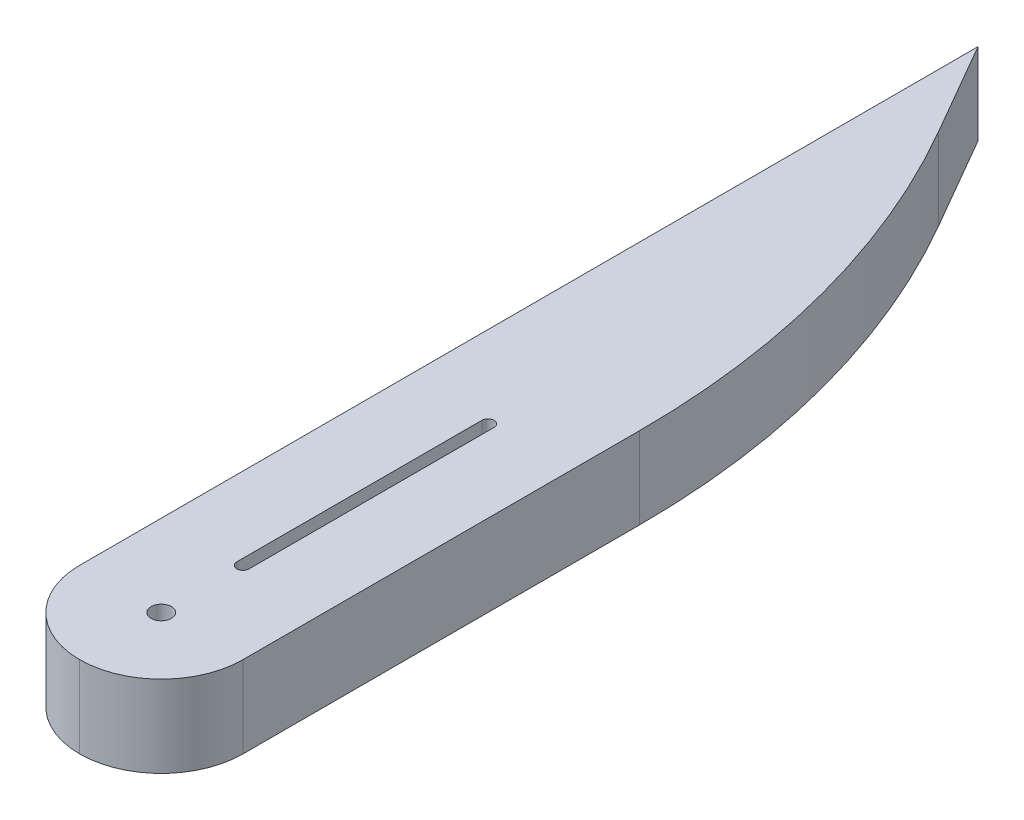
SolidWorks part; units mm, degrees
ref_plane "Front" through (0, 0, 0) normal (0, 0, 1) x (1, 0, 0)
ref_plane "Top" through (0, 0, 0) normal (0, 1, 0) x (1, 0, 0)
ref_plane "Right" through (0, 0, 0) normal (1, 0, 0) x (0, 0, -1)
sketch "Sketch1" plane through (0, 0, 0) normal (0, 0, 1) x (1, 0, 0)
  line L1 (0, 0) -> (-50.8, 0)
  line L2 (0, 0) -> (0, 25.4)
  line L3 (0, 25.4) -> (-50.8, 25.4)
  line L4 (-50.8, 0) -> (-50.8, 25.4)
  dimension "D1" = 50.8
  dimension "D2" = 25.4
extrude "Boss-Extrude1" add sketch "Sketch1" along normal blind 304.8
fillet "Fillet1" radius 25.4 2 edges at (0, 12.7, 304.8) (-50.8, 12.7, 304.8)
sketch "Sketch4" plane through (-50.8, 0, 0) normal (-1, 0, 0) x (0, 0, 1)
  line L0 (0, 25.4) -> (0, 0) construction
  line L1 (304.8, 25.4) -> (279.4, 25.4) construction
  point P0 (0, 12.7)
sketch "Sketch6" plane through (0, 25.4, 0) normal (0, 1, 0) x (1, 0, 0)
  line L0 (-50.8, 0) -> (0, -87.9882)
  line L1 (0, -279.4) -> (0, 0) construction
  line L2 (0, 0) -> (-50.8, 0) construction
  line L3 (0, -87.9882) -> (0, 0)
  line L4 (0, 0) -> (-50.8, 0)
  dimension "D1" = 60
extrude "Cut-Extrude1" cut sketch "Sketch6" against normal through all
fillet "Fillet2" radius 254 1 edges at (0, 12.7, 87.9882)
sketch "Sketch7" plane through (0, 25.4, 0) normal (0, 1, 0) x (1, 0, 0)
  circle A0 centre (-25.4, -279.4) radius 3.175
  arc A1 (-25.4, -304.8) -> (0, -279.4) centre (-25.4, -279.4) ccw construction
  dimension "D1" = 6.35
extrude "Cut-Extrude2" cut sketch "Sketch7" against normal through all
sketch "Sketch8" plane through (0, 25.4, 0) normal (0, 1, 0) x (1, 0, 0)
  line L0 (-27.305, -254) -> (-27.305, -177.8)
  line L1 (-23.495, -254) -> (-23.495, -177.8)
  line L2 (-50.8, -254) -> (0, -254) construction
  line L3 (-50.8, -279.4) -> (-50.8, 0) construction
  line L4 (0, -279.4) -> (0, -156.0473) construction
  arc A0 (-23.495, -177.8) -> (-27.305, -177.8) centre (-25.4, -177.8) ccw
  arc A1 (-27.305, -254) -> (-23.495, -254) centre (-25.4, -254) ccw
  dimension "D1" = 76.2
  dimension "D2" = 3.81
  dimension "D3" = 50.8
extrude "Cut-Extrude3" cut sketch "Sketch8" against normal through all
